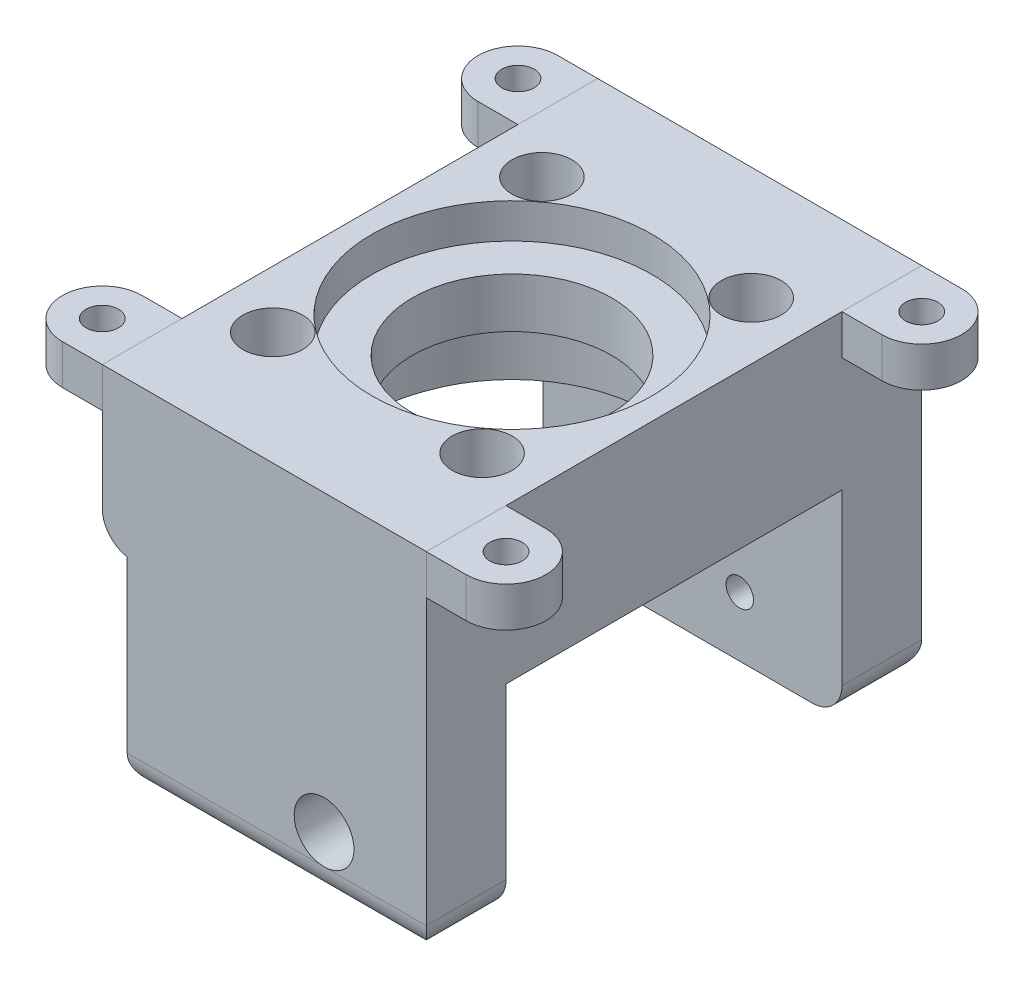
SolidWorks part; units mm, degrees
ref_plane "Front Plane" through (0, 0, 0) normal (0, 0, 1) x (1, 0, 0)
ref_plane "Top Plane" through (0, 0, 0) normal (0, 1, 0) x (1, 0, 0)
ref_plane "Right Plane" through (0, 0, 0) normal (1, 0, 0) x (0, 0, -1)
sketch "Sketch1" plane through (0, 0, 0) normal (0, 1, 0) x (1, 0, 0)
  line L1 (15, -16.85) -> (-15, -16.85)
  line L2 (15, -16.85) -> (15, 16.85)
  line L3 (15, 16.85) -> (-15, 16.85)
  line L4 (-15, -16.85) -> (-15, 16.85)
  line L5 (15, -16.85) -> (-15, 16.85) construction
  line L6 (15, 16.85) -> (-15, -16.85) construction
  circle A0 centre (-11.75, 13.5) radius 1.375
  circle A1 centre (-11.75, -13.5) radius 1.375
  circle A2 centre (9.25, -13.5) radius 1.4608
  circle A3 centre (9.25, 13.5) radius 1.4807
  circle A4 centre (-1.25, 0) radius 14
  point P0 (0, 0)
  dimension "D3" = 27
  dimension "D4" = 2.75
  dimension "D5" = 2.75
  dimension "D6" = 3.35
  dimension "D7" = 3.25
  dimension "D8" = 3.25
  dimension "D9" = 21
  dimension "D10" = 21
  dimension "D11" = 3.35
  dimension "D12" = 3.35
  dimension "D13" = 28
  dimension "D14" = 13.75
  dimension "D1" = 33.7
  dimension "D2" = 30
extrude "Boss-Extrude1" add sketch "Sketch1" along normal blind 15 contours A4 L4 L1 L2 L3 A3 A2 A1 A0 region at (0, 0, 16.3988)
sketch "Sketch2" plane through (0, 15, 0) normal (0, 1, 0) x (1, 0, 0)
  circle A0 centre (-1.25, 0) radius 14
  circle A1 centre (-1.25, 0) radius 10
  dimension "D1" = 20
extrude "Boss-Extrude2" add sketch "Sketch2" against normal blind 8
sketch "Sketch3" plane through (0, 15, 0) normal (0, 1, 0) x (1, 0, 0)
  circle A0 centre (-1.25, 0) radius 14
  circle A1 centre (-1.25, 0) radius 10
extrude "Cut-Extrude1" cut sketch "Sketch3" against normal blind 3
sketch "Sketch5" plane through (0, 15, 0) normal (0, 1, 0) x (1, 0, 0)
  line L1 (15, -16.85) -> (-15, -16.85)
  line L2 (15, -16.85) -> (15, 16.85)
  line L3 (15, 16.85) -> (-15, 16.85)
  line L4 (-15, -16.85) -> (-15, 16.85)
  line L5 (15, -16.85) -> (-15, 16.85) construction
  line L6 (15, 16.85) -> (-15, -16.85) construction
  circle A0 centre (-1.25, 0) radius 14
  circle A1 centre (-11.75, 13.5) radius 1.375
  circle A2 centre (9.25, 13.5) radius 1.4807
  circle A3 centre (9.25, -13.5) radius 1.4608
  circle A4 centre (-11.75, -13.5) radius 1.375
  point P3 (0, 0)
  arc M1 (-15, 2.6339) -> (-15, -2.6339) centre (-1.25, 0) cw
  line M2 (-15, -2.6339) -> (-15, -16.85)
  line M3 (-15, -16.85) -> (15, -16.85)
  line M4 (15, -16.85) -> (15, 16.85)
  line M5 (15, 16.85) -> (-15, 16.85)
  line M6 (-15, 16.85) -> (-15, 2.6339)
  circle M7 centre (9.25, 13.5) radius 1.4807
  circle M8 centre (9.25, -13.5) radius 1.4608
  circle M9 centre (-11.75, -13.5) radius 1.375
  circle M10 centre (-11.75, 13.5) radius 1.375
extrude "Boss-Extrude3" add sketch "Sketch5" along normal blind 0.5 contours M6 M1 M2 M3 M4 M5 M7 M9 M10 M8 region at (0, 15, 16.3988)
sketch "Sketch6" plane through (0, 15.5, 0) normal (0, 1, 0) x (1, 0, 0)
  line L0 (15, 16.85) -> (-15, 16.85) construction
  line L1 (-15, -16.85) -> (15, -16.85) construction
  line L3 (-3.5, 20.35) -> (3.5, 20.35)
  line L4 (-3.5, 20.35) -> (-3.5, -20.35)
  line L5 (-3.5, -20.35) -> (3.5, -20.35)
  line L6 (3.5, 20.35) -> (3.5, -20.35)
  circle A0 centre (0, 20.35) radius 1.625
  circle A1 centre (0, -20.35) radius 1.625
  circle A2 centre (0, 20.35) radius 3.5
  circle A3 centre (0, -20.35) radius 3.5
  line M8 (-15, -16.85) -> (15, -16.85)
  line M10 (15, 16.85) -> (-15, 16.85)
  dimension "D1" = 3.25
  dimension "D2" = 3.25
  dimension "D3" = 7
  dimension "D4" = 7
  dimension "D5" = 3.5
  dimension "D6" = 3.5
extrude "Boss-Extrude4" add sketch "Sketch6" against normal blind 5 contours L3 A2 A0 | A2 L3 A0 | A2 L6 M10 | A2 L4 M10 | A3 L4 M8 | A3 L6 M8 | L5 A3 A1 | L5 A3 A1 region at (0, 15.5, -22.0541) region at (0, 15.5, -18.6459) region at (2.7182, 15.5, -17.6318) region at (-2.7182, 15.5, -17.6318) region at (2.7182, 15.5, 17.6318) region at (0, 15.5, 22.0541) region at (0, 15.5, 18.6459) region at (-2.7182, 15.5, 17.6318)
sketch "Sketch7" plane through (0, 15.5, 0) normal (0, 1, 0) x (1, 0, 0)
  circle A0 centre (-11.75, 13.5) radius 3
  circle A1 centre (9.25, 13.5) radius 3
  circle A2 centre (9.25, -13.5) radius 3
  circle A3 centre (-11.75, -13.5) radius 3
  dimension "D1" = 6
  dimension "D2" = 6
  dimension "D3" = 6
  dimension "D4" = 6
extrude "Cut-Extrude2" cut sketch "Sketch7" against normal blind 12.5
sketch "Sketch8" plane through (0, 15.5, 0) normal (0, 1, 0) x (1, 0, 0)
  circle A0 centre (-1.25, 0) radius 14.05
  dimension "D1" = 28.1
extrude "Cut-Extrude3" cut sketch "Sketch8" against normal blind 3.5
sketch "Sketch9" plane through (0, 0, 0) normal (0, -1, 0) x (1, 0, 0)
  line L0 (-15, 16.85) -> (-15, 2.6339) construction
  line L1 (-15, 24.85) -> (15, 24.85)
  line L2 (-15, 24.85) -> (-15, -24.85)
  line L3 (-15, -24.85) -> (15, -24.85)
  line L4 (15, 24.85) -> (15, -24.85)
  line L5 (15, 16.85) -> (15, -16.85) construction
  line L6 (15, 16.85) -> (-15, 16.85) construction
  line L7 (15, -16.85) -> (-15, -16.85) construction
  line L9 (-15, 16.85) -> (15, 16.85)
  line L10 (-15, 16.85) -> (-15, -16.85)
  line L11 (-15, -16.85) -> (15, -16.85)
  line L12 (15, 16.85) -> (15, -16.85)
  line M7 (-15, -16.85) -> (15, -16.85)
  line M9 (15, 16.85) -> (-15, 16.85)
  dimension "D1" = 0
  dimension "D2" = 0
  dimension "D3" = 8
  dimension "D4" = 8
extrude "Boss-Extrude6" add sketch "Sketch9" along normal blind 20 separate body contours L4 L1 L2 M9 | L4 L2 L3 M7 region at (0, 0, 20.85) region at (0, 0, -20.85)
sketch "Sketch10" plane through (0, 0, 0) normal (0, 1, 0) x (1, 0, 0)
  line L1 (-15, 24.85) -> (15, 24.85)
  line L2 (-15, 24.85) -> (-15, 16.85)
  line L3 (-15, 16.85) -> (15, 16.85)
  line L4 (15, 24.85) -> (15, 16.85)
  line L5 (-15, -16.85) -> (15, -16.85)
  line L6 (-15, -16.85) -> (-15, -24.85)
  line L7 (-15, -24.85) -> (15, -24.85)
  line L8 (15, -16.85) -> (15, -24.85)
extrude "Boss-Extrude7" add sketch "Sketch10" along normal blind 15.5
sketch "Sketch11" plane through (0, 15.5, 0) normal (0, 1, 0) x (1, 0, 0)
  line L0 (-15, -24.85) -> (15, -24.85) construction
  line L1 (-15, 24.85) -> (-17.5, 24.85)
  line L2 (-15, 24.85) -> (-15, -24.85)
  line L3 (-15, -24.85) -> (-17.5, -24.85)
  line L4 (-17.5, 24.85) -> (-17.5, -24.85)
  circle A0 centre (-1.25, 0) radius 14.05
  dimension "D1" = 0
  dimension "D2" = 2.5
sketch "Sketch15" plane through (0, 0, 0) normal (0, -1, 0) x (1, 0, 0)
  line L1 (-17.5, 24.85) -> (-15, 24.85)
  line L2 (-17.5, 24.85) -> (-17.5, -24.85)
  line L3 (-17.5, -24.85) -> (-15, -24.85)
  line L4 (-15, 24.85) -> (-15, -24.85)
  circle A0 centre (-1.25, 0) radius 14
  line M3 (-15, 16.85) -> (-15, 2.6339)
  line M5 (-15, -2.6339) -> (-15, -16.85)
extrude "Boss-Extrude14" add sketch "Sketch15" against normal blind 15.5 contours A0 L4 L1 L2 L3 M3 M5 region at (-16.2582, 0, 0)
sketch "Sketch16" plane through (0, 12, 0) normal (0, 1, 0) x (1, 0, 0)
  circle A0 centre (-1.25, 0) radius 14.05
extrude "Cut-Extrude11" cut sketch "Sketch16" along normal blind 15.5
sketch "Sketch17" plane through (0, 15.5, 0) normal (0, 1, 0) x (1, 0, 0)
  line L0 (-17.5, -24.85) -> (-17.5, 24.85) construction
  line L1 (15, -24.85) -> (15, 24.85) construction
  line L2 (-17.5, -24.85) -> (15, -24.85) construction
  line L3 (15, 24.85) -> (-17.5, 24.85) construction
  line L4 (-21.5, 24.85) -> (19, 24.85)
  line L5 (-21.5, -24.85) -> (19, -24.85)
  line L6 (-21.5, 16.85) -> (19, 16.85)
  line L7 (-21.5, -16.85) -> (19, -16.85)
  circle A0 centre (-21.5, 20.85) radius 1.625
  circle A1 centre (19, 20.85) radius 1.625
  circle A2 centre (-21.5, -20.85) radius 1.625
  circle A3 centre (19, -20.85) radius 1.625
  circle A4 centre (-21.5, 20.85) radius 4
  circle A5 centre (-21.5, -20.85) radius 4
  circle A6 centre (19, -20.85) radius 4
  circle A7 centre (19, 20.85) radius 4
  line M4 (-17.5, 24.85) -> (-17.5, -24.85)
  line M6 (15, -24.85) -> (15, 24.85)
  dimension "D1" = 3.25
  dimension "D2" = 3.25
  dimension "D3" = 3.25
  dimension "D4" = 3.25
  dimension "D5" = 8
  dimension "D6" = 8
  dimension "D7" = 8
  dimension "D8" = 8
  dimension "D9" = 4
  dimension "D10" = 4
  dimension "D11" = 4
  dimension "D12" = 4
  dimension "D13" = 4
  dimension "D14" = 4
  dimension "D15" = 4
  dimension "D16" = 4
extrude "Boss-Extrude15" add sketch "Sketch17" against normal blind 4 separate body contours A4 A0 | A5 L7 M4 | A5 L5 M4 | A5 A2 | A6 L7 M6 | A6 A3 | A6 L5 M6 | A7 A1 | A7 L4 M6 | A7 L6 M6 | A4 L6 M4 | A4 L4 M4 region at (-18.3935, 15.5, -23.9565) region at (-18.7516, 15.5, -23.5984) region at (-18.3935, 15.5, -17.7435) region at (15.8935, 15.5, -23.9565) region at (21.7484, 15.5, -23.5984) region at (15.8935, 15.5, -17.7435) region at (-18.3935, 15.5, 17.7435) region at (15.8935, 15.5, 17.7435) region at (-18.7516, 15.5, 18.1016) region at (-18.3935, 15.5, 23.9565) region at (21.7484, 15.5, 18.1016) region at (15.8935, 15.5, 23.9565)
sketch "Sketch18" plane through (0, 0, -24.85) normal (0, 0, -1) x (-1, 0, 0)
  line L0 (15, 0) -> (-15, 0) construction
  line L2 (-15, 15.5) -> (-15, -20) construction
  circle A0 centre (-4.75, -14) radius 1.375
  dimension "D1" = 2.75
  dimension "D2" = 14
  dimension "D3" = 10.25
extrude "Cut-Extrude12" cut sketch "Sketch18" against normal blind 55.5
sketch "Sketch19" plane through (0, 0, 24.85) normal (0, 0, 1) x (1, 0, 0)
  circle A0 centre (4.75, -14) radius 3
  dimension "D1" = 6
extrude "Cut-Extrude13" cut sketch "Sketch19" against normal blind 5
sketch "Sketch20" plane through (0, 0, -24.85) normal (0, 0, -1) x (-1, 0, 0)
  circle A0 centre (-4.75, -14) radius 3
  dimension "D1" = 6
extrude "Cut-Extrude14" cut sketch "Sketch20" against normal blind 5
fillet "Fillet1" radius 3 1 edges at (-17.5, 0, 0)
fillet "Fillet2" radius 3 6 edges at (0, -20, 24.85) (0, -20, -24.85) (15, -20, 20.85) (15, -20, -20.85) (-15, -20, -20.85) (-15, -20, 20.85)
